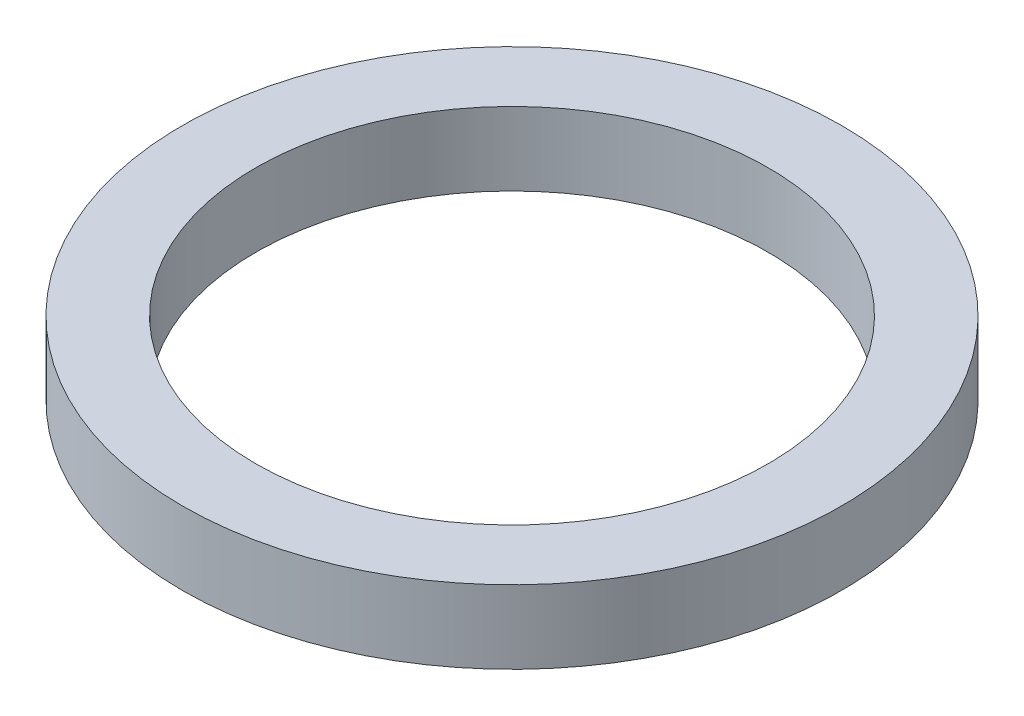
SolidWorks part; units mm, degrees
ref_plane "Front Plane" through (0, 0, 0) normal (0, 0, 1) x (1, 0, 0)
ref_plane "Top Plane" through (0, 0, 0) normal (0, 1, 0) x (1, 0, 0)
ref_plane "Right Plane" through (0, 0, 0) normal (1, 0, 0) x (0, 0, -1)
sketch "Sketch1" plane through (0, 0, 0) normal (0, 1, 0) x (1, 0, 0)
  circle A0 centre (0, 0) radius 45
  dimension "FLANGE_OD" = 90
extrude "Boss-Extrude1" add sketch "Sketch1" along normal blind 10
sketch "Sketch2" plane through (0, 0, 0) normal (0, 1, 0) x (1, 0, 0)
  circle A0 centre (0, 0) radius 35
  dimension "BORE_D" = 70
extrude "Cut-Extrude1" cut sketch "Sketch2" along normal through all
sketch "Sketch3" plane through (0, 10, 0) normal (0, 1, 0) x (1, 0, 0)
  circle A0 centre (0, 0) radius 20.1938 construction
  circle A1 centre (-20.1938, 0) radius 1.6115
  dimension "BOLT_D" = 3.223
  dimension "BOLT_PCD" = 40.3876
extrude "Cut-Extrude2" cut sketch "Sketch3" against normal blind 6.9246 rebuild error yes
pattern_circular "CirPattern1" count 4 over 360 rebuild error yes
